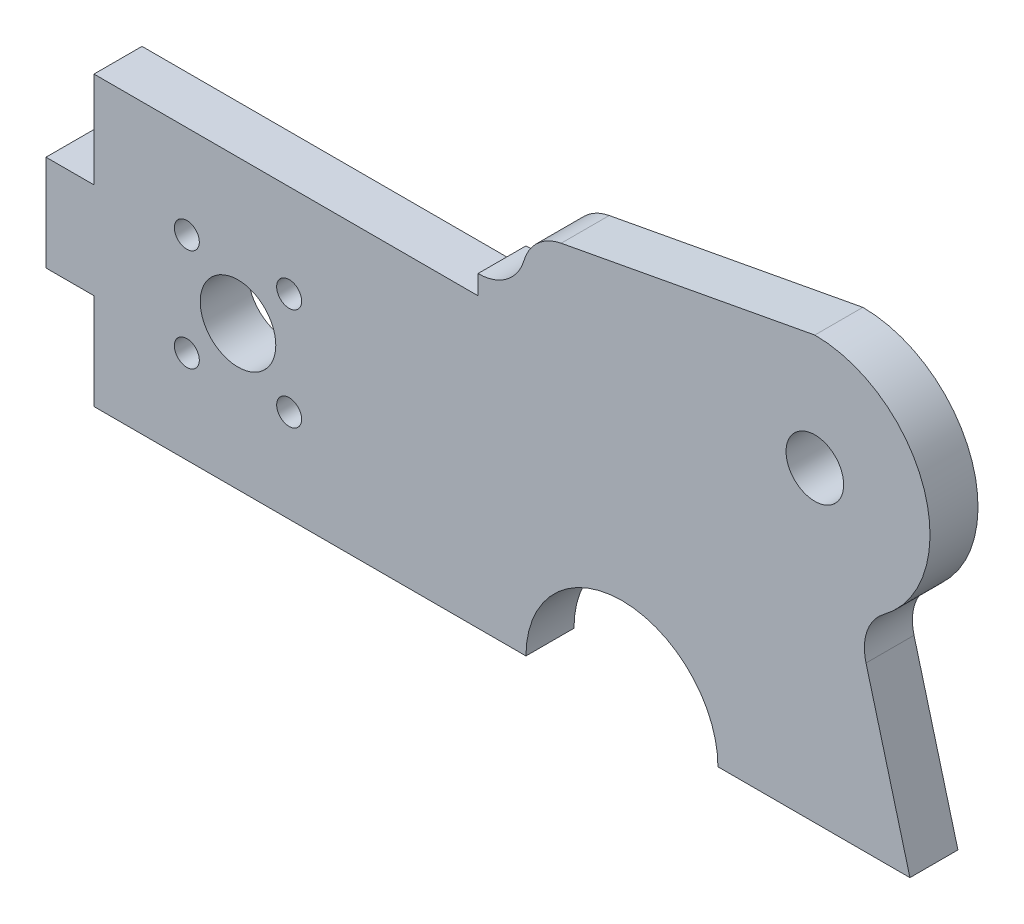
SolidWorks part; units mm, degrees
ref_plane "Front Plane" through (0, 0, 0) normal (0, 0, 1) x (1, 0, 0)
ref_plane "Top Plane" through (0, 0, 0) normal (0, 1, 0) x (1, 0, 0)
ref_plane "Right Plane" through (0, 0, 0) normal (1, 0, 0) x (0, 0, -1)
sketch "Sketch1" plane through (0, 0, 0) normal (0, 0, 1) x (1, 0, 0)
  line L0 (0, 0) -> (107.95, 0)
  line L3 (0, 38.1) -> (0, 25.4)
  line L4 (95.3675, 55.88) -> (0, 38.1)
  line L5 (0, 19.05) -> (100.2273, 19.05) construction
  line L6 (19.05, 19.05) -> (19.05, 28.62) construction
  line L7 (19.05, 19.05) -> (25.817, 25.817) construction
  line L8 (107.95, 0) -> (100.9363, 26.1756)
  line L10 (0, 12.7) -> (0, 0)
  line L11 (0, 25.4) -> (-6.35, 25.4)
  line L13 (0, 12.7) -> (-6.35, 12.7)
  line L14 (-6.35, 25.4) -> (-6.35, 12.7)
  line L15 (100.9363, 26.1756) -> (100.8688, 26.4276)
  arc A0 (100.8688, 26.4276) -> (95.3675, 55.88) centre (95.3675, 40.64) ccw
  circle A1 centre (95.3675, 40.64) radius 3.81
  circle A2 centre (19.05, 19.05) radius 9.57 construction
  circle A3 centre (25.817, 25.817) radius 1.651
  circle A4 centre (25.817, 12.283) radius 1.651
  circle A5 centre (12.283, 12.283) radius 1.651
  circle A6 centre (12.283, 25.817) radius 1.651
  point P26 (19.05, 19.05)
  dimension "D1" = 7.62
  dimension "D5" = 15.24
  dimension "D4" = 19.14
  dimension "D7" = 3.302
  dimension "D11" = 97.0107
  dimension "D2" = 38.1
  dimension "D3" = 40.64
  dimension "D6" = 107.95
  dimension "D8" = 45
  dimension "D9" = 4
  dimension "D10" = 19.05
  dimension "D12" = 75
  dimension "D14" = 12.7
  dimension "D15" = 12.7
  dimension "D16" = 6.35
extrude "Boss-Extrude1" add sketch "Sketch1" along normal blind 6.35
sketch "Sketch2" plane through (0, 0, 6.35) normal (0, 0, 1) x (1, 0, 0)
  circle A0 centre (95.3675, 40.64) radius 38.1 construction
sketch "Sketch3" plane through (0, 0, 0) normal (-1, 0, 0) x (0, 0, 1)
  line L0 (0, 38.1) -> (6.35, 25.4) construction
  line L1 (6.35, 12.7) -> (0, 0) construction
  circle A0 centre (3.175, 31.75) radius 1.5875
  circle A1 centre (3.175, 6.35) radius 1.5875
  dimension "D1" = 3.175
  dimension "D2" = 3.175
extrude "Cut-Extrude1" cut sketch "Sketch3" against normal blind 6.35
sketch "Sketch6" plane through (0, 0, 6.35) normal (0, 0, 1) x (1, 0, 0)
  line L0 (0, 0) -> (107.95, 0) construction
  line L1 (57.15, 0) -> (82.55, 0)
  arc A0 (82.55, 0) -> (57.15, 0) centre (69.85, 0) ccw
  dimension "D1" = 25.4
  dimension "D2" = 25.4
extrude "Cut-Extrude2" cut sketch "Sketch6" against normal blind 6.35
sketch "Sketch7" plane through (0, 0, 6.35) normal (0, 0, 1) x (1, 0, 0)
  line L0 (12.283, 25.817) -> (25.817, 12.283) construction
  line L1 (12.283, 12.283) -> (25.817, 25.817) construction
  circle A0 centre (19.05, 19.05) radius 5
  dimension "D1" = 10
extrude "Cut-Extrude3" cut sketch "Sketch7" against normal through all
fillet "Fillet1" radius 6.35 1 edges at (100.8688, 26.4276, 3.175)
sketch "Sketch8" plane through (0, 0, 6.35) normal (0, 0, 1) x (1, 0, 0)
  line L1 (0, 38.1) -> (50.8, 38.1)
  line L2 (0, 38.1) -> (0, 50.8)
  line L3 (0, 50.8) -> (50.8, 50.8)
  line L4 (50.8, 38.1) -> (50.8, 50.8)
  dimension "D1" = 50.8
  dimension "D2" = 12.7
extrude "Cut-Extrude4" cut sketch "Sketch8" against normal blind 50.8
sketch "Sketch9" plane through (0, 0, 6.35) normal (0, 0, 1) x (1, 0, 0)
  line L3 (50.8, 40.64) -> (57.15, 40.64)
  line L5 (57.15, 40.64) -> (50.8, 40.64)
  line L6 (57.15, 40.64) -> (57.15, 50.8)
  line L7 (57.15, 50.8) -> (50.8, 50.8)
  line L8 (50.8, 40.64) -> (50.8, 50.8)
  line L9 (0, 38.1) -> (50.8, 38.1) construction
  line M8 (50.8, 47.571) -> (50.8, 38.1)
  line M21 (95.3675, 55.88) -> (50.8, 47.571)
  dimension "D1" = 10.16
  dimension "D2" = 2.54
  dimension "D3" = 6.35
extrude "Cut-Extrude5" cut sketch "Sketch9" against normal blind 19.304 contours L3 L6 M21 M8 region at (54.0583, 44.4092, 6.35)
fillet "Fillet6" radius 6.35 1 edges at (57.15, 40.64, 3.175)
fillet "Fillet7" radius 6.35 1 edges at (57.15, 48.7549, 3.175)
